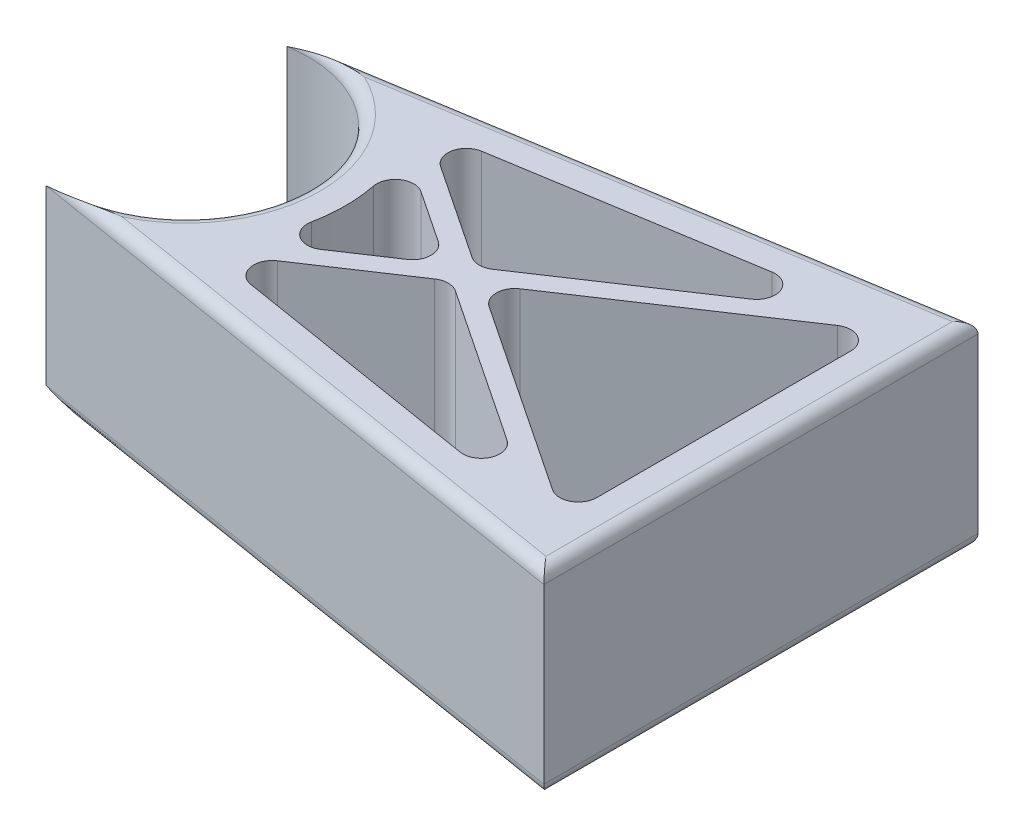
SolidWorks part; units mm, degrees
material "Carbon Fiber"
ref_plane "Front Plane" through (0, 0, 0) normal (0, 0, 1) x (1, 0, 0)
ref_plane "Top Plane" through (0, 0, 0) normal (0, 1, 0) x (1, 0, 0)
ref_plane "Right Plane" through (0, 0, 0) normal (1, 0, 0) x (0, 0, -1)
sketch "Sketch1" plane through (0, 0, 0) normal (0, 1, 0) x (1, 0, 0)
  circle A0 centre (0, 0) radius 7.9
  circle A1 centre (0, 0) radius 6.6
  dimension "D1" = 1.3
  dimension "D2" = 15.8
extrude "Boss-Extrude1" add sketch "Sketch1" along normal blind 1043.94
sketch "Sketch2" plane through (0, 1043.94, 0) normal (0, 1, 0) x (1, 0, 0)
  line L7 (63.3412, -12.5413) -> (38.2588, 12.5412) construction
  line L8 (59.6011, -11.3411) -> (41.9989, -11.3411)
  line L9 (62.1411, -8.8011) -> (62.1411, 8.8011)
  line L10 (59.6011, 11.3411) -> (41.9989, 11.3411)
  line L12 (59.6011, 8.8011) -> (41.9989, -8.8011) construction
  line L13 (37.8518, 15.0484) -> (-1.4083, 8.6754)
  line L14 (63.3412, -15.0813) -> (38.2587, -15.0813)
  line L15 (65.8812, -12.5413) -> (65.8812, 12.5412)
  line L16 (63.3412, 15.0812) -> (38.2588, 15.0812)
  line L19 (-1.2658, 7.7979) -> (37.1729, 14.0376)
  line L20 (37.1729, -14.0376) -> (-1.2658, -7.7979)
  line L22 (-1.4083, -8.6754) -> (37.8518, -15.0484)
  line L23 (39.4589, -8.8011) -> (39.4589, 8.8011)
  line L25 (37.1729, 14.0376) -> (37.1729, -14.0376)
  arc A3 (38.2587, -15.0813) -> (37.8518, -15.0484) centre (38.2587, -12.5413) cw
  arc A4 (37.8518, 15.0484) -> (38.2588, 15.0812) centre (38.2588, 12.5412) cw
  arc A5 (63.3412, 15.0812) -> (65.8812, 12.5412) centre (63.3412, 12.5412) cw
  arc A6 (65.8812, -12.5413) -> (63.3412, -15.0813) centre (63.3412, -12.5413) cw
  arc A7 (62.1411, 8.8011) -> (59.6011, 11.3411) centre (59.6011, 8.8011) ccw
  arc A8 (41.9989, 11.3411) -> (39.4589, 8.8011) centre (41.9989, 8.8011) ccw
  arc A9 (39.4589, -8.8011) -> (41.9989, -11.3411) centre (41.9989, -8.8011) ccw
  arc A10 (59.6011, -11.3411) -> (62.1411, -8.8011) centre (59.6011, -8.8011) ccw
  arc A11 (37.8518, 15.0484) -> (38.2588, 15.0812) centre (38.2588, 12.5412) cw
  circle A12 centre (0, 0) radius 7.9 construction
  arc A14 (38.2587, -15.0813) -> (37.8518, -15.0484) centre (38.2587, -12.5413) cw
  arc A15 (-1.4083, -8.6754) -> (-1.4083, 8.6754) centre (0, 0) cw
  arc A16 (-1.2658, 7.7979) -> (-1.2658, -7.7979) centre (0, 0) ccw
  point P0 (50.8, 0)
  point P16 (-0.3814, 7.1278)
  point P17 (38.888, 9.2291)
  point P18 (52.551, -21.1077)
  point P19 (-0.3814, -7.1278)
  circle M3 centre (0, 0) radius 7.9
  dimension "D3" = 2.54
  dimension "D1" = 22.6822
  dimension "D4" = 50.8
  dimension "D2" = 30.1625
  dimension "D5" = 0.889
  dimension "D6" = 0.889
  dimension "D7" = 2.286
  dimension "D8" = 0.889
extrude "Boss-Extrude2" add sketch "Sketch2" against normal up to surface (1043.94 mm away) contours A6 L15 A5 L16 A4 L13 L19 L25 L20 L22 A3 L14 A10 L8 A9 L23 A8 L10 A7 L9 M3 region at (38.1193, 1043.94, -14.2703) up to face at (0, 0, 7.9)
sketch "Sketch3" plane through (0, 1043.94, 0) normal (0, 1, 0) x (1, 0, 0)
  line L0 (37.1729, -14.0376) -> (-1.2658, -7.7979) construction
  line L1 (37.1729, 14.0376) -> (37.1729, -14.0376) construction
  line L3 (-1.2658, 7.7979) -> (37.1729, 14.0376)
  line L4 (37.1729, -14.0376) -> (-1.2658, -7.7979)
  line L5 (37.1729, 14.0376) -> (37.1729, -14.0376)
  arc A0 (-1.2658, -7.7979) -> (-1.2658, 7.7979) centre (0, 0) ccw construction
  arc A3 (-1.2658, -7.7979) -> (-1.2658, 7.7979) centre (0, 0) ccw
  point P10 (37.1729, 11.8619)
  point P12 (37.9942, -14.1709)
extrude "Boss-Extrude3" add sketch "Sketch3" along normal blind 12.7 separate body
delete or keep bodies "Body-Delete/Keep 1" type keep bodies bodies 105
sketch "Sketch4" plane through (0, 1056.64, 0) normal (0, 1, 0) x (1, 0, 0)
  line L3 (-1.2658, -7.7979) -> (37.1729, -14.0376)
  line L4 (37.1729, -14.0376) -> (37.1729, 14.0376)
  line L5 (37.1729, 14.0376) -> (-1.2658, 7.7979)
  line L6 (-1.2658, -7.7979) -> (37.1729, -14.0376) construction
  line L7 (37.1729, -14.0376) -> (37.1729, 14.0376) construction
  line L8 (37.1729, 14.0376) -> (-1.2658, 7.7979) construction
  line L9 (34.4206, -11.7449) -> (35.1252, -10.6883)
  line L10 (34.4206, -11.7449) -> (7.3626, 6.296)
  line L11 (35.1252, -10.6883) -> (8.0671, 7.3527)
  line L12 (7.3626, 6.296) -> (8.0671, 7.3527)
  line L13 (37.1729, 0) -> (7.9, 0) construction
  line L14 (35.1252, 10.6883) -> (8.0671, -7.3527)
  line L15 (7.3626, -6.296) -> (8.0671, -7.3527)
  line L16 (34.4206, 11.7449) -> (7.3626, -6.296)
  line L17 (34.4206, 11.7449) -> (35.1252, 10.6883)
  line L18 (7.7148, -6.8243) -> (34.7729, -11.2166)
  line L19 (34.7729, -11.2166) -> (34.7729, 11.2166)
  line L20 (34.7729, 11.2166) -> (7.7148, 6.8243)
  line L21 (37.1729, -14.0376) -> (37.1729, 14.0376) construction
  arc A3 (-1.2658, -7.7979) -> (-1.2658, 7.7979) centre (0, 0) ccw
  arc A4 (7.7148, -6.8243) -> (7.7148, 6.8243) centre (0, 0) ccw
  arc A5 (-1.2658, -7.7979) -> (-1.2658, 7.7979) centre (0, 0) ccw construction
  arc A6 (-1.2658, -7.7979) -> (-1.2658, 7.7979) centre (0, 0) ccw construction
  point P7 (34.7729, -11.2166)
  point P8 (7.7148, -6.8243)
  point P18 (7.7148, 6.8243)
  dimension "D3" = 1.27
  dimension "D1" = 0
  dimension "D2" = 2.4
extrude "Cut-Extrude1" cut sketch "Sketch4" against normal through all contours L11 L19 L14 | L14 L18 L10 | A4 L16 L10 | L16 L20 L11 region at (19.9484, 1056.64, 6.236) region at (29.5468, 1056.64, 0) region at (12.173, 1056.64, 0) region at (19.9484, 1056.64, -6.236)
fillet "Fillet1" radius 1.2 12 edges at (19.0947, 1050.29, 0) (17.9501, 1050.29, -0.7632) (16.8054, 1050.29, 0) (17.9501, 1050.29, 0.7632) (8.6354, 1050.29, 6.9738) (33.2599, 1050.29, 10.971) (8.6354, 1050.29, -6.9738) (8.8152, 1050.29, -5.3274) (8.8152, 1050.29, 5.3274) (33.2599, 1050.29, -10.971) (34.7729, 1050.29, -10.4534) (34.7729, 1050.29, 10.4534)
fillet "Fillet2" radius 0.76 8 edges at (17.9535, 1056.64, -10.9178) (37.1729, 1056.64, 0) (17.9535, 1056.64, 10.9178) (7.9, 1056.64, 0) (7.9, 1043.94, 0) (17.9535, 1043.94, 10.9178) (37.1729, 1043.94, 0) (17.9535, 1043.94, -10.9178)
equation "\"D6@Sketch2\"=\"D5@Sketch2\""
equation "\"D8@Sketch2\"=\"D5@Sketch2\""
